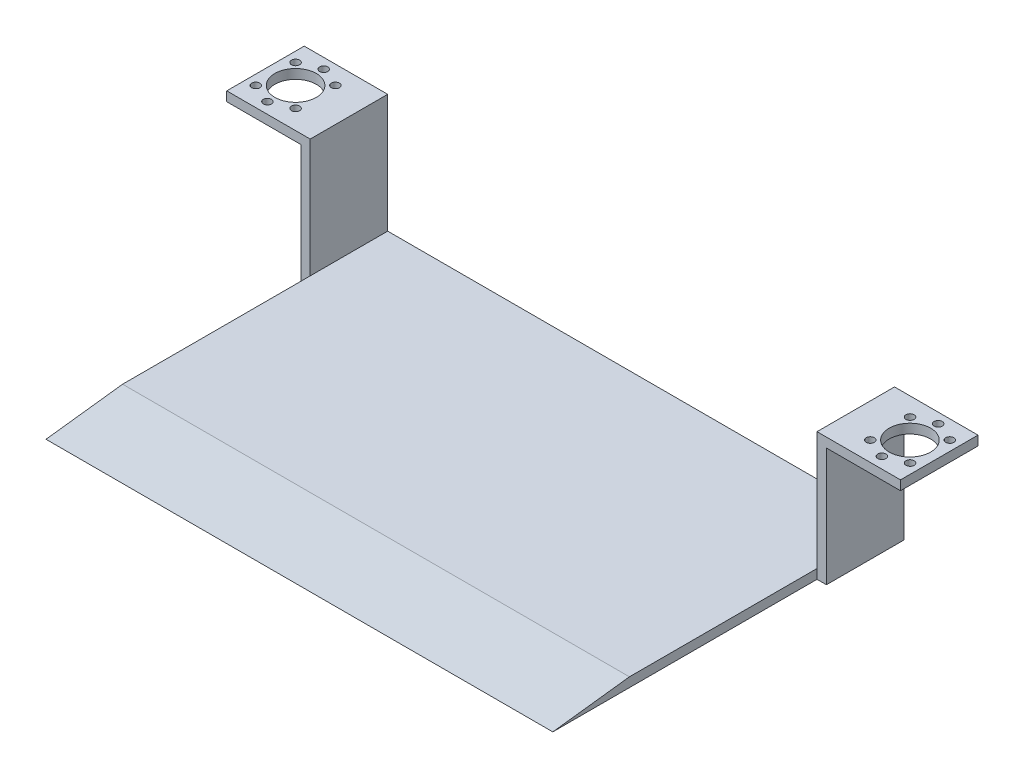
SolidWorks part; units mm, degrees
ref_plane "Front Plane" through (0, 0, 0) normal (0, 0, 1) x (1, 0, 0)
ref_plane "Top Plane" through (0, 0, 0) normal (0, 1, 0) x (1, 0, 0)
ref_plane "Right Plane" through (0, 0, 0) normal (1, 0, 0) x (0, 0, -1)
sketch "Sketch1" plane through (0, 0, 0) normal (0, 1, 0) x (1, 0, 0)
  line L1 (0, 0) -> (454.914, 0)
  line L2 (0, 0) -> (0, 381)
  line L3 (0, 381) -> (454.914, 381)
  line L4 (454.914, 0) -> (454.914, 381)
  dimension "D1" = 454.914
  dimension "D2" = 381
extrude "Boss-Extrude1" add sketch "Sketch1" along normal blind 86.36
sketch "Sketch3" plane through (0, 86.36, 0) normal (0, 1, 0) x (1, 0, 0)
  line L1 (454.914, 0) -> (404.9014, 0)
  line L2 (454.914, 0) -> (454.914, 202.0062)
  line L3 (454.914, 202.0062) -> (404.9014, 202.0062)
  line L4 (404.9014, 0) -> (404.9014, 202.0062)
  line L5 (0, 0) -> (50.0126, 0)
  line L6 (0, 0) -> (0, 202.0062)
  line L7 (0, 202.0062) -> (50.0126, 202.0062)
  line L8 (50.0126, 0) -> (50.0126, 202.0062)
  dimension "D1" = 202.0062
  dimension "D2" = 50.0126
  dimension "D3" = 202.0062
  dimension "D4" = 50.0126
extrude "Cut-Extrude1" cut sketch "Sketch3" against normal through all
sketch "Sketch4" plane through (0, 86.36, 0) normal (0, 1, 0) x (1, 0, 0)
  line L0 (454.914, 381) -> (0, 381) construction
  line L1 (0, 381) -> (0, 202.0062) construction
  line L2 (454.914, 202.0062) -> (454.914, 381) construction
  circle A0 centre (20.066, 355.092) radius 14
  circle A1 centre (434.848, 355.092) radius 14
  dimension "D1" = 28
  dimension "D4" = 28
  dimension "D5" = 20.066
  dimension "D6" = 25.908
  dimension "D2" = 25.908
  dimension "D3" = 20.066
extrude "Cut-Extrude2" cut sketch "Sketch4" against normal through all
sketch "Sketch5" plane through (0, 86.36, 0) normal (0, 1, 0) x (1, 0, 0)
  line L0 (454.914, 381) -> (0, 381) construction
  line L1 (56.3626, 381) -> (398.5514, 381)
  line L2 (56.3626, 381) -> (56.3626, 0)
  line L3 (56.3626, 0) -> (398.5514, 0)
  line L4 (398.5514, 381) -> (398.5514, 0)
  line L5 (50.0126, 0) -> (404.9014, 0) construction
  line L6 (50.0126, 0) -> (50.0126, 202.0062) construction
  line L7 (404.9014, 202.0062) -> (404.9014, 0) construction
  dimension "D1" = 6.35
  dimension "D2" = 6.35
extrude "Cut-Extrude3" cut sketch "Sketch5" against normal blind 80.01
sketch "Sketch6" plane through (454.914, 0, 0) normal (1, 0, 0) x (0, 0, -1)
  line L0 (381, 86.36) -> (381, 0) construction
  line L1 (202.0062, 0) -> (381, 0)
  line L2 (202.0062, 0) -> (202.0062, 79.9974)
  line L3 (202.0062, 79.9974) -> (381, 79.9974)
  line L4 (381, 0) -> (381, 79.9974)
  dimension "D1" = 79.9974
extrude "Cut-Extrude4" cut sketch "Sketch6" against normal blind 50.0126
sketch "Sketch7" plane through (0, 0, 0) normal (-1, 0, 0) x (0, 0, 1)
  line L0 (-202.0062, 0) -> (-202.0062, 86.36) construction
  line L1 (-381, 0) -> (-202.0062, 0)
  line L2 (-381, 0) -> (-381, 79.9974)
  line L3 (-381, 79.9974) -> (-202.0062, 79.9974)
  line L4 (-202.0062, 0) -> (-202.0062, 79.9974)
  dimension "D1" = 79.9974
extrude "Cut-Extrude5" cut sketch "Sketch7" against normal blind 50.0126
sketch "Sketch10" plane through (404.9014, 0, 0) normal (1, 0, 0) x (0, 0, -1)
  line L0 (0, 0) -> (202.0062, 0)
  line L1 (202.0062, 86.36) -> (0, 86.36) construction
  line L3 (202.0062, 86.36) -> (202.0062, 0)
  line L5 (381, 0) -> (0, 0) construction
  line L8 (202.0062, 86.36) -> (0, 86.36)
  line L9 (0, 86.36) -> (0, 0)
  line L10 (202.0062, 79.9974) -> (202.0062, 86.36) construction
  point P1 (160.8307, 0)
extrude "Cut-Extrude6" cut sketch "Sketch10" against normal through all
sketch "Sketch11" plane through (0, 86.36, 0) normal (0, 1, 0) x (1, 0, 0)
  line L0 (434.848, 385.1807) -> (434.848, 325.1677) construction
  line L1 (457.9437, 355.092) -> (408.0384, 355.092) construction
  line L2 (434.848, 355.1742) -> (453.5332, 373.8594) construction
  line L3 (434.848, 355.1742) -> (419.9379, 370.0843) construction
  line L4 (434.848, 355.1742) -> (452.7645, 337.2577) construction
  line L5 (434.848, 355.1742) -> (417.2384, 337.5646) construction
  circle A1 centre (434.848, 374.1742) radius 2.75
  circle A2 centre (448.283, 368.6092) radius 2.75
  circle A3 centre (421.413, 368.6092) radius 2.75
  circle A4 centre (448.283, 341.7392) radius 2.75
  circle A5 centre (434.848, 336.1742) radius 2.75
  circle A6 centre (421.413, 341.7392) radius 2.75
  dimension "D2" = 45
  dimension "D5" = 5.5
  dimension "D6" = 5.5
  dimension "D7" = 5.5
  dimension "D8" = 5.5
  dimension "D9" = 5.5
  dimension "D10" = 5.5
  dimension "D3" = 45
  dimension "D4" = 45
extrude "Cut-Extrude7" cut sketch "Sketch11" against normal through all
sketch "Sketch12" plane through (0, 86.36, 0) normal (0, 1, 0) x (1, 0, 0)
  line L0 (20.066, 355.092) -> (20.066, 379.9549) construction
  line L1 (20.066, 355.092) -> (42.2706, 355.092) construction
  line L2 (20.066, 355.092) -> (20.066, 337.1345) construction
  line L3 (20.066, 355.092) -> (2.8652, 355.092) construction
  line L4 (20.066, 355.092) -> (38.3107, 373.3367) construction
  line L5 (20.066, 355.092) -> (33.6036, 341.5544) construction
  line L6 (20.066, 355.092) -> (5.5449, 369.6131) construction
  line L7 (20.066, 355.092) -> (7.0967, 342.1227) construction
  circle A1 centre (20.066, 374.092) radius 2.75
  circle A2 centre (6.631, 368.527) radius 2.75
  circle A3 centre (33.501, 368.527) radius 2.75
  circle A4 centre (33.501, 341.657) radius 2.75
  circle A5 centre (20.066, 336.092) radius 2.75
  circle A6 centre (6.631, 341.657) radius 2.75
  dimension "D5" = 5.5
  dimension "D6" = 5.5
  dimension "D7" = 5.5
  dimension "D8" = 5.5
  dimension "D9" = 5.5
  dimension "D10" = 5.5
  dimension "D1" = 45
  dimension "D2" = 45
  dimension "45" = 45
  dimension "D3" = 45
extrude "Cut-Extrude8" cut sketch "Sketch12" against normal through all
sketch "Sketch13" plane through (398.5514, 0, 0) normal (1, 0, 0) x (0, 0, -1)
  line L0 (202.0062, 0) -> (150.2896, 0)
  line L1 (150.2896, 0) -> (202.0062, 6.35)
  line L2 (202.0062, 0) -> (202.0062, 79.9974) construction
  line L3 (202.0062, 6.35) -> (202.0062, 0)
  dimension "D1" = 7
  dimension "D2" = 6.35
extrude "Boss-Extrude2" add sketch "Sketch13" against normal up to surface (342.1888 mm away) up to face at (56.3626, 46.355, -291.5031)
sketch "Sketch15" plane through (0, 86.36, 0) normal (0, 1, 0) x (1, 0, 0)
  line L0 (398.5514, 328.676) -> (454.914, 328.676) construction
  line L1 (398.5514, 202.0062) -> (398.5514, 381) construction
  line L2 (454.914, 202.0062) -> (454.914, 381) construction
  line L3 (454.914, 381) -> (398.5514, 381) construction
  line L4 (0, 328.676) -> (56.3626, 328.676) construction
  line L5 (398.5514, 328.676) -> (454.914, 328.676)
  line L6 (398.5514, 328.676) -> (398.5514, 202.0062)
  line L7 (398.5514, 202.0062) -> (454.914, 202.0062)
  line L8 (454.914, 328.676) -> (454.914, 202.0062)
  line L9 (0, 381) -> (0, 202.0062) construction
  line L10 (56.3626, 381) -> (56.3626, 202.0062) construction
  line L11 (56.3626, 381) -> (0, 381) construction
  line L13 (56.3626, 202.0062) -> (0, 202.0062)
  line L14 (56.3626, 202.0062) -> (56.3626, 328.676)
  line L15 (56.3626, 328.676) -> (0, 328.676)
  line L16 (0, 202.0062) -> (0, 328.676)
  dimension "D1" = 52.324
  dimension "D2" = 52.324
extrude "Cut-Extrude9" cut sketch "Sketch15" against normal through all
